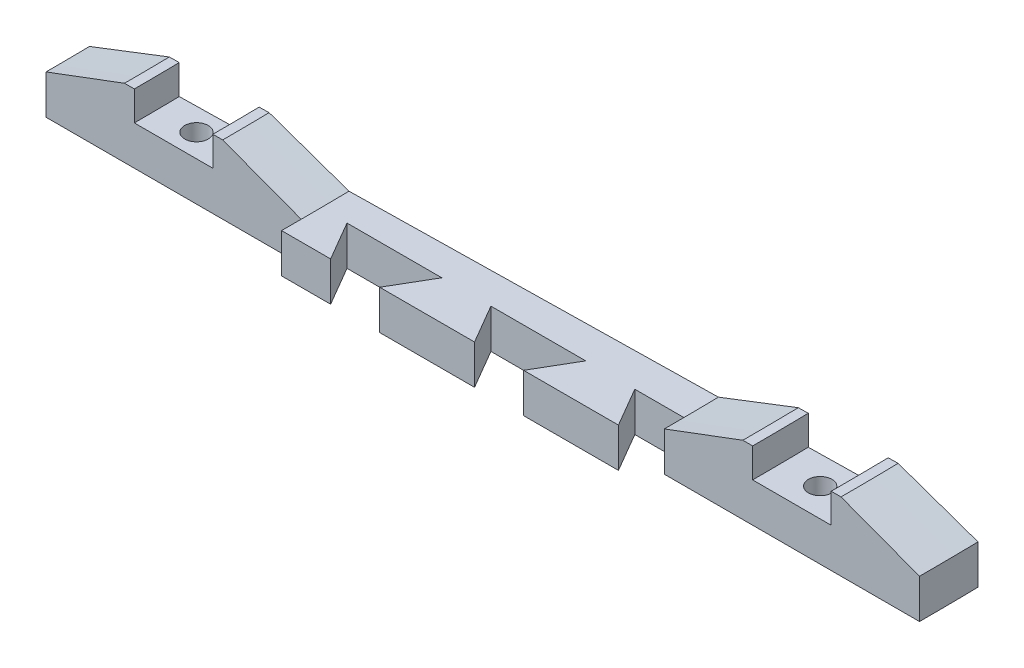
SolidWorks part; units mm, degrees
other "标注1"
sketch "草图3" plane through (-22.25, 4, -10) normal (-0.231, 0.6469, -0.7268) x (-0.9696, -0.2151, 0.1167)
ref_plane "前视基准面" through (0, 0, 0) normal (0, 0, 1) x (1, 0, 0)
ref_plane "上视基准面" through (0, 0, 0) normal (0, 1, 0) x (1, 0, 0)
ref_plane "右视基准面" through (0, 0, 0) normal (1, 0, 0) x (0, 0, -1)
other "Configuration Table"
sketch "草图4" plane through (0, 0, 0) normal (0, 0, 1) x (1, 0, 0)
  line L6 (8.5, -1.5) -> (17.75, -1.5)
  line L11 (17.75, -1.5) -> (17.75, -3.5)
  line L16 (17.75, -3.5) -> (-4.5, -3.5)
  line L17 (-4.5, -3.5) -> (-4.5, -1.5)
  line L19 (0, 0) -> (0, -1.5)
  line L20 (0, -1.5) -> (4, -1.5)
  line L21 (4, -1.5) -> (4, 0)
  line L26 (4, 0) -> (4.5, 0)
  line L27 (4.5, 0) -> (8.5, -1.5)
  line L28 (0, 0) -> (-0.5, 0)
  line L29 (-0.5, 0) -> (-4.5, -1.5)
  dimension "D2" = 4
  dimension "D4" = 0.5
  dimension "D5" = 2
  dimension "D6" = 2
  dimension "D7" = 4
  dimension "D8" = 1.5
  dimension "D9" = 4
  dimension "D10" = 22.25
extrude "凸台-拉伸1" add sketch "草图4" along normal blind 2.5 contours L28 L29 L17 L16 L11 L6 L27 L26 L21 L20 L19 | L19 | L21 region at (5.9579, -2.2764, 0)
sketch "草图5" plane through (0, -1.5, 0) normal (0, 1, 0) x (1, 0, 0)
  line L0 (0, 0) -> (4, -2.5) construction
  line L1 (0, -2.5) -> (0, 0) construction
  line L2 (0, -2.5) -> (4, -2.5) construction
  line L3 (4, -2.5) -> (4, 0) construction
  line L4 (0, 0) -> (4, 0) construction
  circle A0 centre (2, -1.25) radius 0.6
  circle A1 centre (2, -1.25) radius 1
  dimension "D1" = 1.2
  dimension "D2" = 2
extrude "切除-拉伸1" cut sketch "草图5" against normal through all contours A0
extrude "切除-拉伸2" cut sketch "草图5<3>" along normal blind 1 from surface contours A1 starting at face at (2, -3.5, 1.85)
sketch "草图5<3>" plane through (0, -1.5, 0) normal (0, 1, 0) x (1, 0, 0) same geometry as "草图5"
mirror "镜向1" about plane through (17.75, 0, 2.5) normal (1, 0, 0) of bodies 215
sketch "草图6" plane through (0, 0, 2.5) normal (0, 0, 1) x (1, 0, 0)
  line L18 (0, 0) -> (-0.5, 0)
  line L19 (-0.5, 0) -> (-4.5, -1.5)
  line L20 (-4.5, -1.5) -> (-4.5, -3.5)
  line L21 (-4.5, -3.5) -> (40, -3.5)
  line L22 (40, -3.5) -> (40, -1.5)
  line L23 (40, -1.5) -> (36, 0)
  line L24 (36, 0) -> (35.5, 0)
  line L25 (35.5, 0) -> (35.5, -1.5)
  line L26 (35.5, -1.5) -> (31.5, -1.5)
  line L27 (31.5, -1.5) -> (31.5, 0)
  line L28 (31.5, 0) -> (31, 0)
  line L29 (31, 0) -> (27, -1.5)
  line L30 (27, -1.5) -> (8.5, -1.5)
  line L31 (8.5, -1.5) -> (4.5, 0)
  line L32 (4.5, 0) -> (4, 0)
  line L33 (4, 0) -> (4, -1.5)
  line L34 (4, -1.5) -> (0, -1.5)
  line L35 (0, -1.5) -> (0, 0)
  line L36 (0, 0) -> (-0.5, 0)
  line L37 (-0.5, 0) -> (-4.5, -1.5)
  line L38 (-4.5, -1.5) -> (-4.5, -3.5)
  line L39 (-4.5, -3.5) -> (40, -3.5)
  line L40 (40, -3.5) -> (40, -1.5)
  line L41 (40, -1.5) -> (36, 0)
  line L42 (36, 0) -> (35.5, 0)
  line L43 (35.5, 0) -> (35.5, -1.5)
  line L44 (35.5, -1.5) -> (31.5, -1.5)
  line L45 (31.5, -1.5) -> (31.5, 0)
  line L46 (31.5, 0) -> (31, 0)
  line L47 (31, 0) -> (27, -1.5)
  line L48 (27, -1.5) -> (8.5, -1.5)
  line L49 (8.5, -1.5) -> (4.5, 0)
  line L50 (4.5, 0) -> (4, 0)
  line L51 (4, 0) -> (4, -1.5)
  line L52 (4, -1.5) -> (0, -1.5)
  line L53 (0, -1.5) -> (0, 0)
  dimension "D1" = 0
sketch "草图8" plane through (0, 0, 2.5) normal (0, 0, 1) x (1, 0, 0)
  line L0 (-132.25, 94.8536) -> (-132.25, -34.2886)
  line L1 (17.75, -1.5) -> (17.75, -3.5)
  line L2 (27, -1.5) -> (8.5, -1.5) construction
  line L3 (-4.5, -3.5) -> (40, -3.5) construction
  dimension "D1" = 150
revolve "旋转1" add sketch "草图6" angle 1 about L0
sketch "草图9" plane through (0, -1.5, 0) normal (0, 1, 0) x (1, 0, 0)
  line L0 (-0.005, -3.6541) -> (3.9948, -3.689) construction
  line L1 (3.9948, -3.689) -> (31.4938, -3.929) construction
  line L2 (31.4938, -3.929) -> (35.4936, -3.9639) construction
  arc A0 (-0.0201, -4.8081) -> (0, -2.5) centre (-132.25, -2.5) ccw construction
  arc A1 (3.9792, -4.8779) -> (4, -2.5) centre (-132.25, -2.5) ccw construction
  arc A2 (31.4751, -5.3578) -> (31.5, -2.5) centre (-132.25, -2.5) ccw construction
  arc A3 (35.4745, -5.4276) -> (35.5, -2.5) centre (-132.25, -2.5) ccw construction
  circle A4 centre (1.9949, -3.6715) radius 1
  circle A5 centre (1.9949, -3.6715) radius 0.6
  circle A6 centre (33.4937, -3.9464) radius 1
  circle A7 centre (33.4937, -3.9464) radius 0.6
  dimension "D1" = 2
  dimension "D2" = 1.2
extrude "切除-拉伸3" cut sketch "草图9" against normal through all contours A7 | A5
extrude "切除-拉伸4" cut sketch "草图9<3>" along normal blind 1 from surface contours A6 | A4 starting at face at (32.8937, -3.5, 3.9464)
sketch "草图9<3>" plane through (0, -1.5, 0) normal (0, 1, 0) x (1, 0, 0) same geometry as "草图9"
ref_plane "基准面1" through (0, 0, 0) normal (0, 0, -1) x (-1, 0, 0)
mirror "镜向2" about plane through (0, 0, 0) normal (0, 0, 1) of bodies 219
sketch "草图10" plane through (0, 0, 0) normal (0, 0, -1) x (-1, 0, 0)
  line L1 (-56.5264, 9.7873) -> (16.8069, 9.7873)
  line L2 (-56.5264, 9.7873) -> (-56.5264, -18.7129)
  line L3 (-56.5264, -18.7129) -> (16.8069, -18.7129)
  line L4 (16.8069, 9.7873) -> (16.8069, -18.7129)
extrude "切除-拉伸5" cut sketch "草图10" against normal through all
sketch "草图11" plane through (0, -1.5, 0) normal (0, 1, 0) x (1, 0, 0)
  line L0 (8.5, 2.5) -> (8.5, 1.5)
  line L1 (8.5, 0) -> (8.5, 2.5) construction
  line L2 (8.5, 1.5) -> (11, 1.5)
  line L3 (11, 1.5) -> (9.8344, 3.5)
  line L4 (9.8344, 3.5) -> (14.6656, 3.5)
  line L5 (14.6656, 3.5) -> (13.5, 1.5)
  line L6 (13.5, 1.5) -> (18.3312, 1.5)
  line L7 (18.3312, 1.5) -> (17.1656, 3.5)
  line L8 (17.1656, 3.5) -> (21.9969, 3.5)
  line L9 (21.9969, 3.5) -> (20.8312, 1.5)
  line L10 (20.8312, 1.5) -> (25.6625, 1.5)
  line L11 (25.6625, 1.5) -> (24.4969, 3.5)
  line L12 (24.4969, 3.5) -> (26.9969, 3.5)
  line L13 (26.9969, 3.5) -> (27, 2.5)
  line L14 (11, 1.5) -> (13.5, 1.5) construction
  line L15 (14.6656, 3.5) -> (17.1656, 3.5) construction
  line L16 (18.3312, 1.5) -> (20.8312, 1.5) construction
  line L17 (21.9969, 3.5) -> (24.4969, 3.5) construction
  line L18 (12.25, 3.5) -> (12.25, 1.5) construction
  line L19 (8.5, 2.5) -> (12.25, 2.5) construction
  line L20 (8.5, 2.5) -> (-4.5, 2.5)
  line L21 (-4.5, 2.5) -> (-4.5, 0)
  line L22 (55, 0) -> (-55, 0) construction
  line L23 (-4.5, 0) -> (-4.5, 2.5) construction
  line L24 (-4.5, 0) -> (40, 0)
  line L25 (40, 0) -> (40, 2.5)
  line L26 (40, 2.5) -> (27, 2.5)
  arc A0 (27, 2.5) -> (26.9757, 5.2793) centre (-132.25, 2.5) ccw construction
  dimension "D1" = 2
  dimension "D2" = 2.5
extrude "切除-拉伸8" cut sketch "草图11" against normal through all both and the other way through all
